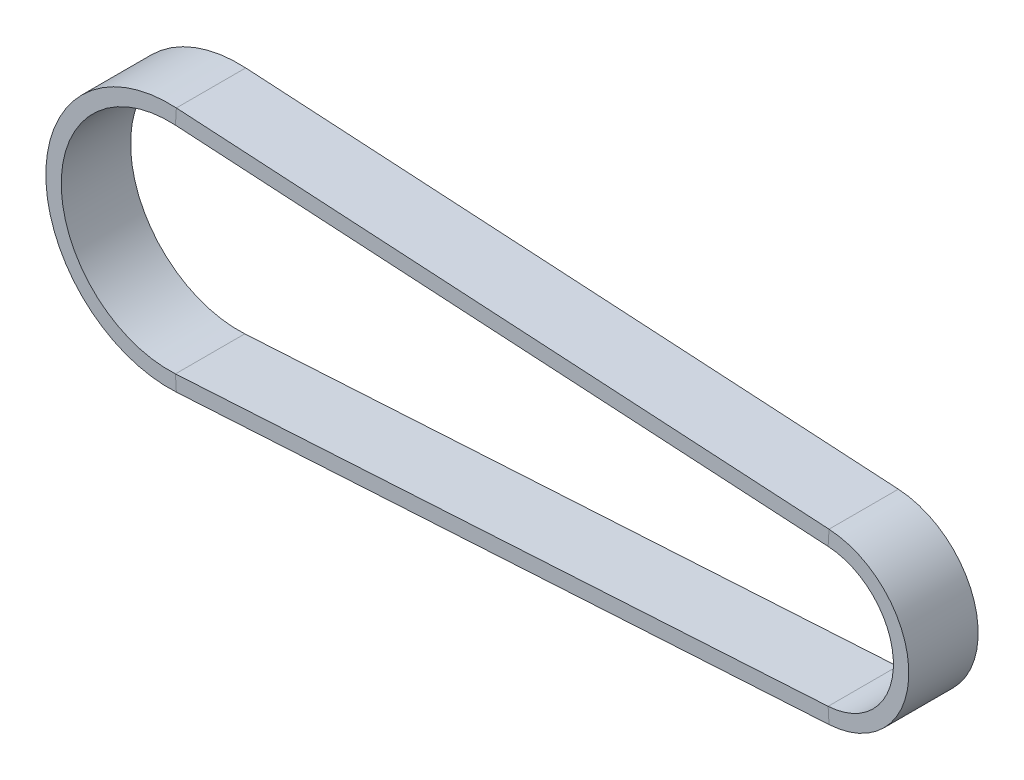
SolidWorks part; units mm, degrees
ref_plane "Ebene vorne" through (0, 0, 0) normal (0, 0, 1) x (1, 0, 0)
ref_plane "Ebene oben" through (0, 0, 0) normal (0, 1, 0) x (1, 0, 0)
ref_plane "Ebene rechts" through (0, 0, 0) normal (1, 0, 0) x (0, 0, -1)
sketch "Skizze2" plane through (0, 0, 0) normal (0, 1, 0) x (1, 0, 0)
  line L0 (-14, -20) -> (-16, -20) construction
  line L1 (-16, -11) -> (-16, -20) construction
  line L2 (-14, -11) -> (-16, -11) construction
  line L3 (-14, -11) -> (-14, -20) construction
  line L4 (-14, -20) -> (-16, -20)
  line L5 (-16, -11) -> (-16, -20)
  line L6 (-14, -11) -> (-16, -11)
  line L7 (-14, -11) -> (-14, -20)
ref_plane "Ebene1" through (0, 0, 15.5) normal (0, 0, 1) x (1, 0, 0)
sketch "Skizze3" plane through (0, 0, 15.5) normal (0, 0, 1) x (1, 0, 0)
  line L1 (0, 0) -> (-25, 0) construction
  line L2 (0, 0) -> (450, 0) construction
  line L3 (0.8824, 14.974) -> (85.5882, 9.9827)
  arc A1 (-15, 0) -> (0.8824, 14.974) centre (0, 0) cw
  arc A3 (95, 0) -> (85.5882, 9.9827) centre (85, 0) ccw
  dimension "D1" = 10
  dimension "D2" = 15
sweep "Austragung1" add profiles "Skizze2" path "Skizze3"
mirror "Spiegeln1" about plane through (0, 0, 0) normal (0, -1, 0) of bodies 101
